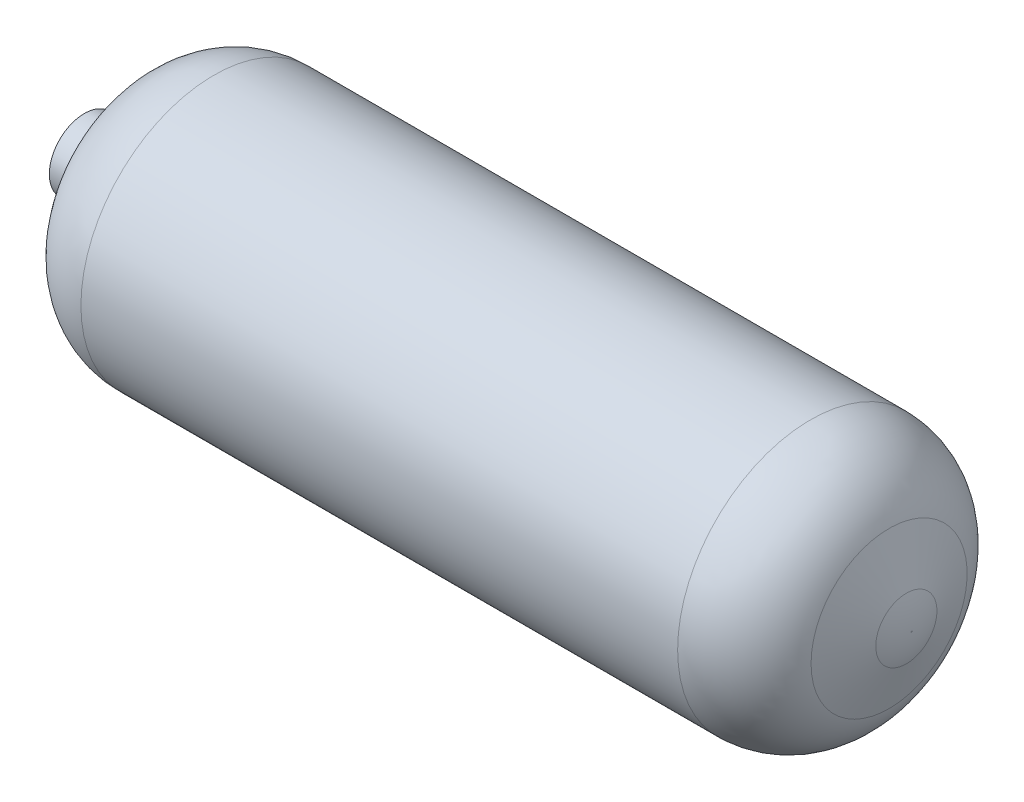
SolidWorks part; units mm, degrees
material "6061-T6 (SS)"
ref_plane "Front Plane" through (0, 0, 0) normal (0, 0, 1) x (1, 0, 0)
ref_plane "Top Plane" through (0, 0, 0) normal (0, 1, 0) x (1, 0, 0)
ref_plane "Right Plane" through (0, 0, 0) normal (1, 0, 0) x (0, 0, -1)
sketch "Sketch1" plane through (0, 0, 0) normal (0, 0, 1) x (1, 0, 0)
  line L0 (-0.2756, 0.129) -> (0.3032, 0.129)
  line L1 (-0.4012, 0.034) -> (-0.4012, 0)
  line L2 (-0.4012, 0.034) -> (-0.3773, 0.034)
  line L4 (-0.3729, 0.0367) -> (-0.3487, 0.0842)
  line L5 (-0.4012, 0) -> (0.4012, 0) construction
  line L6 (0.3794, 0.0757) -> (0.3961, 0.0297)
  line L7 (-0.4012, 0) -> (0.4012, 0)
  line L8 (0.4012, 0) -> (0.4012, 0.0006)
  arc A0 (-0.2756, 0.129) -> (-0.3487, 0.0842) centre (-0.2756, 0.047) ccw
  arc A1 (0.3032, 0.129) -> (0.3794, 0.0757) centre (0.3032, 0.048) cw
  arc A2 (0.4012, 0.0006) -> (0.3961, 0.0297) centre (0.3163, 0.0006) ccw
  arc A3 (-0.3729, 0.0367) -> (-0.3773, 0.034) centre (-0.3773, 0.039) cw
  point P6 (-0.3742, 0.034)
  dimension "D8" = 0.082
  dimension "D11" = 0.081
  dimension "D13" = 0.085
  dimension "D6" = 0.005
  dimension "D2" = 0.2756
  dimension "D3" = 0.034
  dimension "D4" = 0.3032
  dimension "D5" = 0.027
  dimension "D7" = 117
  dimension "D9" = 0.8025
  dimension "D10" = 110
revolve "Revolve2" add sketch "Sketch1" angle 360 about L7 region at (0.0088, 0.062, 0)
scale "Scale1" scale about origin uniform scaling yes scale factor 649.767462
shell "Shell2" thickness 5.588
sketch "Sketch2" plane through (0, 0, 0) normal (0, 1, 0) x (1, 0, 0)
  line L7 (246.4991, 49.1898) -> (257.3884, 19.2716)
  line L8 (260.7192, 0.3818) -> (197.042, 0.3818)
  line L9 (197.042, -83.82) -> (197.042, 83.82) construction
  line L10 (197.042, 0.3818) -> (197.042, 83.82)
  line L11 (-226.5465, 54.7281) -> (-242.2713, 23.8664)
  line L12 (-260.7192, 22.0921) -> (-245.1667, 22.0921)
  line L13 (-260.7192, 22.0921) -> (-260.7192, 0)
  line L14 (-260.7192, 22.0921) -> (-260.7192, -22.0921) construction
  line L15 (-260.7192, 0) -> (-179.0728, 0)
  line L16 (-179.0728, -83.82) -> (-179.0728, 83.82) construction
  line L17 (-179.0728, 0) -> (-179.0728, 83.82)
  arc A2 (197.042, 83.82) -> (246.4991, 49.1898) centre (197.042, 31.1888) cw
  arc A3 (257.3884, 19.2716) -> (260.7192, 0.3818) centre (205.489, 0.3818) cw
  arc A4 (-179.0728, 83.82) -> (-226.5465, 54.7281) centre (-179.0728, 30.5391) ccw
  arc A5 (-242.2713, 23.8664) -> (-245.1667, 22.0921) centre (-245.1667, 25.3417) cw
revolve "Added to make cavity cut for shoulder" [suppressed] add sketch "Sketch2" angle 360 about L15
sketch "Sketch3" plane through (-260.7192, 0, 0) normal (-1, 0, 0) x (0, 0, 1)
  circle A0 centre (0, 0) radius 111.5906
  circle A1 centre (0, 0) radius 46.355
  dimension "D1" = 92.71
